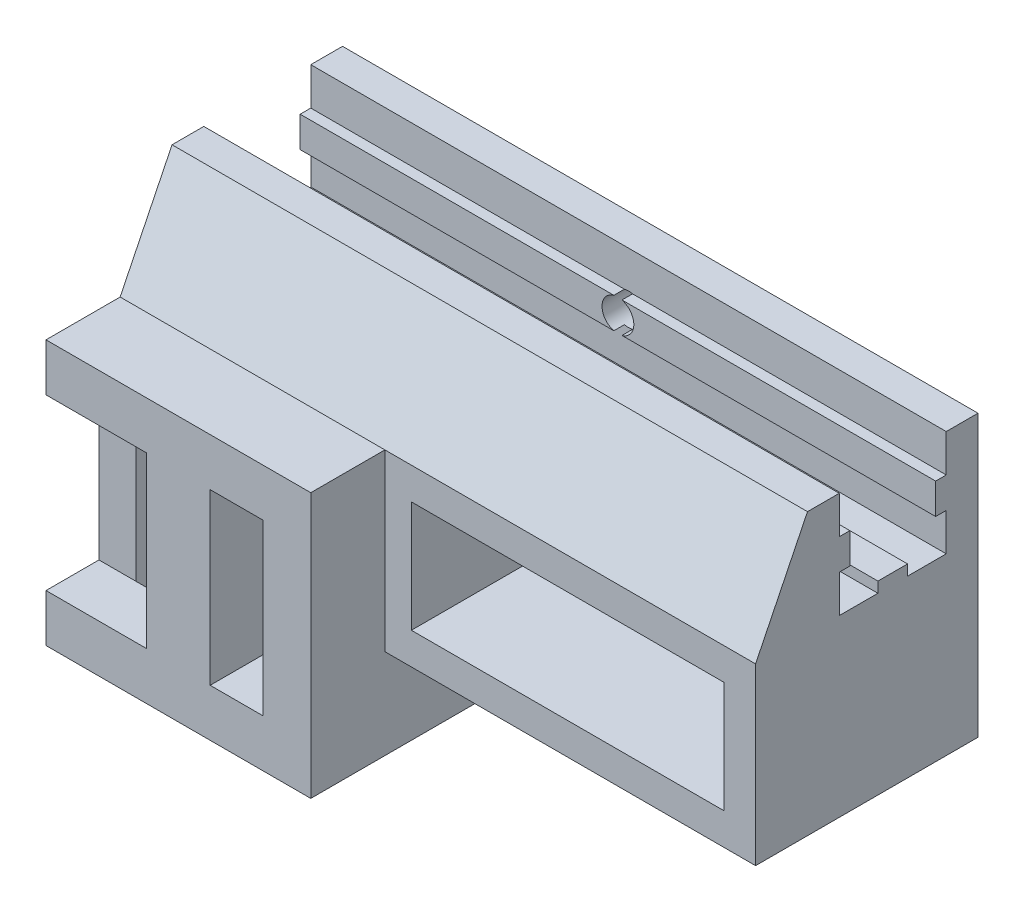
SolidWorks part; units mm, degrees
ref_plane "Front Plane" through (0, 0, 0) normal (0, 0, 1) x (1, 0, 0)
ref_plane "Top Plane" through (0, 0, 0) normal (0, 1, 0) x (1, 0, 0)
ref_plane "Right Plane" through (0, 0, 0) normal (1, 0, 0) x (0, 0, -1)
sketch "Esquisse1" plane through (0, 0, 0) normal (0, 0, 1) x (1, 0, 0)
  line L1 (-30, 17.5) -> (30, 17.5)
  line L2 (-30, 17.5) -> (-30, -17.5)
  line L3 (-30, -17.5) -> (30, -17.5)
  line L4 (30, 17.5) -> (30, -17.5)
  point P4 (-30, 0)
  point P6 (0, 17.5)
  dimension "D1" = 35
  dimension "D2" = 60
extrude "Boss.-Extru.1" add sketch "Esquisse1" along normal blind 3
sketch "Esquisse2" plane through (0, 0, 3) normal (0, 0, 1) x (1, 0, 0)
  line L0 (-30, 17.5) -> (-30, -17.5) construction
  line L1 (-30, 11.05) -> (30, 11.05)
  line L2 (-30, 11.05) -> (-30, 13.95)
  line L3 (-30, 13.95) -> (30, 13.95)
  line L4 (30, 11.05) -> (30, 13.95)
  line L5 (30, -17.5) -> (30, 17.5) construction
  line L6 (30, 17.5) -> (-30, 17.5) construction
  point P8 (-30, 12.5)
  dimension "D1" = 5
  dimension "D2" = 2.9
extrude "Boss.-Extru.2" add sketch "Esquisse2" along normal blind 1
sketch "Esquisse3" plane through (0, 0, 0) normal (0, 0, -1) x (-1, 0, 0)
  line L0 (-30, 11.05) -> (-30, 13.95) construction
  line L1 (-30, 17.5) -> (30, 17.5) construction
  circle A0 centre (0, 12.5) radius 1.5
  point P2 (0, 0)
  point P5 (0, 0)
  point P6 (-30, 12.5)
  point P9 (0, 17.5)
  dimension "D1" = 3
extrude "Enlèv. mat.-Extru.1" cut sketch "Esquisse3" against normal through all
sketch "Esquisse4" plane through (0, 0, 3) normal (0, 0, 1) x (1, 0, 0)
  line L0 (-30, -17.5) -> (30, -17.5) construction
  line L1 (-30, -17.5) -> (-5, -17.5)
  line L2 (-30, -17.5) -> (-30, 7.5)
  line L3 (-30, 7.5) -> (-5, 7.5)
  line L4 (-5, -17.5) -> (-5, 7.5)
  line L5 (-30, 11.05) -> (-30, -17.5) construction
  line L6 (30, 17.5) -> (-30, 17.5) construction
  line L7 (-26.5, 4) -> (-8.5, 4)
  line L8 (-26.5, 4) -> (-26.5, -14)
  line L9 (-26.5, -14) -> (-8.5, -14)
  line L10 (-8.5, 4) -> (-8.5, -14)
  point P6 (-17.5, 4)
  point P13 (-17.5, 7.5)
  point P14 (-26.5, -5)
  point P15 (-30, -5)
  point P16 (-1.3429, 6.1571)
  dimension "D1" = 10
  dimension "D2" = 18
  dimension "D3" = 3.5
extrude "Boss.-Extru.3" add sketch "Esquisse4" along normal blind 20
sketch "Esquisse5" plane through (0, 0, 23) normal (0, 0, 1) x (1, 0, 0)
  line L1 (-26.5, 4) -> (-8.5, 4)
  line L2 (-26.5, 4) -> (-26.5, -14)
  line L3 (-26.5, -14) -> (-8.5, -14)
  line L4 (-8.5, 4) -> (-8.5, -14)
extrude "Enlèv. mat.-Extru.2" cut sketch "Esquisse5" against normal through all and the other way through all
sketch "Esquisse6" plane through (0, 0, 23) normal (0, 0, 1) x (1, 0, 0)
  line L0 (-5, 7.5) -> (-30, 7.5) construction
  line L1 (-30, -17.5) -> (-5, -17.5)
  line L2 (-5, -17.5) -> (-5, 7.5)
  line L4 (-30, 7.5) -> (-30, 3)
  line L5 (-30, -17.5) -> (-5, -17.5) construction
  line L6 (-8.5, 4) -> (-26.5, 4) construction
  line L7 (-9.5, 3) -> (-30, 3)
  line L8 (-9.5, 3) -> (-9.5, -13)
  line L9 (-9.5, -13) -> (-30, -13)
  line L12 (-8.5, -14) -> (-8.5, 4) construction
  line L13 (-30, -13) -> (-30, -17.5)
  line L15 (-5, 7.5) -> (-30, 7.5)
  line L16 (-30, 7.5) -> (-30, -17.5) construction
  point P11 (-17.5, 7.5)
  dimension "D2" = 1
  dimension "D3" = 1
extrude "Boss.-Extru.4" add sketch "Esquisse6" along normal blind 5
sketch "Esquisse7" plane through (0, 0, 28) normal (0, 0, 1) x (1, 0, 0)
  line L0 (-5, 7.5) -> (-30, 7.5) construction
  line L1 (-20.5, 7.5) -> (-14.5, 7.5)
  line L2 (-20.5, 7.5) -> (-20.5, -17.5)
  line L3 (-20.5, -17.5) -> (-14.5, -17.5)
  line L4 (-14.5, 7.5) -> (-14.5, -17.5)
  line L5 (-30, -17.5) -> (-5, -17.5) construction
  line L6 (-26.5, 3) -> (-26.5, -13) construction
  dimension "D1" = 6
  dimension "D2" = 6
extrude "Boss.-Extru.5" add sketch "Esquisse7" against normal up to surface (5 mm away) up to face at (-28.25, -5, 23)
sketch "Esquisse8" plane through (0, 0, 0) normal (0, 0, -1) x (-1, 0, 0)
  line L0 (5, -17.5) -> (5, 7.5) construction
  line L1 (2.5, -6) -> (-27, -6)
  line L2 (2.5, -6) -> (2.5, 4.5)
  line L3 (2.5, 4.5) -> (-27, 4.5)
  line L4 (-27, -6) -> (-27, 4.5)
  line L5 (-30, 17.5) -> (30, 17.5) construction
  dimension "D1" = 10.5
  dimension "D2" = 29.5
  dimension "D3" = 2.5
  dimension "D4" = 13
extrude "Enlèv. mat.-Extru.3" cut sketch "Esquisse8" against normal through all
sketch "Esquisse10" plane through (0, 0, 3) normal (0, 0, 1) x (1, 0, 0)
  line L0 (-5, -17.5) -> (-5, 7.5) construction
  line L1 (-5, -9) -> (30, -9)
  line L2 (-5, -9) -> (-5, 7.5)
  line L3 (-5, 7.5) -> (30, 7.5)
  line L4 (30, -9) -> (30, 7.5)
  line L6 (-2.5, -6) -> (27, -6) construction
  line L7 (27, -6) -> (27, 4.5) construction
  line L8 (30, -17.5) -> (30, 11.05) construction
  line L9 (-2.5, -6) -> (27, -6)
  line L10 (-2.5, -6) -> (-2.5, 4.5)
  line L11 (-2.5, 4.5) -> (27, 4.5)
  line L12 (27, -6) -> (27, 4.5)
  line L13 (-5, 7.5) -> (-30, 7.5) construction
  point P17 (19.5, 7.5)
  point P19 (31.7939, 11.05)
  dimension "D1" = 3
  dimension "D2" = 3
extrude "Boss.-Extru.6" add sketch "Esquisse10" along normal blind 18
sketch "Esquisse11" plane through (0, 0, 3) normal (0, 0, 1) x (1, 0, 0)
  line L1 (-5, -9) -> (30, -9)
  line L2 (-5, -9) -> (-5, -17.5)
  line L3 (-5, -17.5) -> (30, -17.5)
  line L4 (30, -9) -> (30, -17.5)
extrude "Enlèv. mat.-Extru.4" cut sketch "Esquisse11" against normal through all
sketch "Esquisse12" plane through (0, 7.5, 0) normal (0, 1, 0) x (1, 0, 0)
  line L0 (30, -21) -> (30, -3) construction
  line L1 (-30, -9.45) -> (30, -9.45)
  line L2 (-30, -9.45) -> (-30, -6.65)
  line L3 (-30, -6.65) -> (30, -6.65)
  line L4 (30, -9.45) -> (30, -6.65)
  line L5 (-30, -28) -> (-30, -3) construction
  point P6 (-30, -9.9391)
  point P9 (-30, -8.05)
  dimension "D1" = 2.8
  dimension "D2" = 5.05
extrude "Boss.-Extru.7" add sketch "Esquisse12" along normal blind 1
sketch "Esquisse13" plane through (30, 0, 0) normal (1, 0, 0) x (0, 0, -1)
  line L0 (-4, 13.95) -> (-3, 13.95) construction
  line L1 (-21, 7.5) -> (-9.45, 7.5) construction
  line L2 (-4, 11.05) -> (-3, 11.05) construction
  line L3 (-13.1, 7.5) -> (-13.1, 11.05)
  line L4 (-13.1, 11.05) -> (-12.1, 11.05)
  line L5 (-12.1, 11.05) -> (-12.1, 13.95)
  line L6 (-12.1, 13.95) -> (-13.1, 13.95)
  line L7 (-13.1, 13.95) -> (-13.1, 17.5)
  line L8 (-13.1, 17.5) -> (-16.1, 17.5)
  line L9 (-16.1, 17.5) -> (-16.1, 7.5)
  line L10 (-16.1, 7.5) -> (-13.1, 7.5)
  line L12 (-3, 7.5) -> (-3, 11.05) construction
  line L13 (-3, 17.5) -> (0, 17.5) construction
  point P1 (-13.7997, 7.5)
  point P5 (-12.6, 13.95)
  dimension "D1" = 10.1
extrude "Boss.-Extru.8" add sketch "Esquisse13" against normal through all
sketch "Esquisse14" plane through (30, 0, 0) normal (1, 0, 0) x (0, 0, -1)
  line L0 (-16.1, 7.5) -> (-16.1, 17.5)
  line L1 (-16.1, 17.5) -> (-16.1, 7.5) construction
  line L2 (-16.1, 17.5) -> (-21, 7.5)
  line L3 (-21, 7.5) -> (-16.1, 7.5)
  point P7 (-16.1, 17.5)
extrude "Boss.-Extru.9" add sketch "Esquisse14" against normal through all
